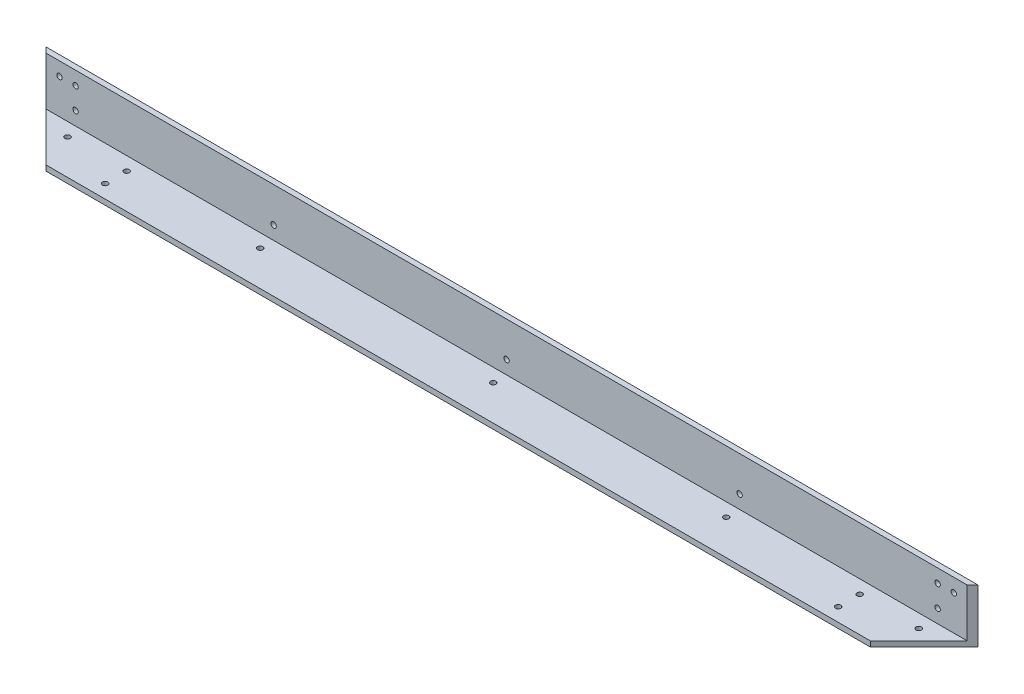
SolidWorks part; units mm, degrees
ref_plane "Front Plane" through (0, 0, 0) normal (0, 0, 1) x (1, 0, 0)
ref_plane "Top Plane" through (0, 0, 0) normal (0, 1, 0) x (1, 0, 0)
ref_plane "Right Plane" through (0, 0, 0) normal (1, 0, 0) x (0, 0, -1)
sketch "Sketch1" plane through (0, 0, 0) normal (1, 0, 0) x (0, 0, -1)
  line L0 (0, 0) -> (-31.75, 0)
  line L1 (-31.75, 0) -> (-31.75, 3.175)
  line L2 (-31.75, 3.175) -> (-3.175, 3.175)
  line L3 (-3.175, 3.175) -> (-3.175, 31.75)
  line L4 (-3.175, 31.75) -> (0, 31.75)
  line L5 (0, 31.75) -> (0, 0)
  dimension "LHeight" = 31.75
  dimension "LWidth" = 31.75
  dimension "LMaterialThickness" = 3.175
  dimension "D1" = 28.575
  dimension "D2" = 28.575
  dimension "D3" = 3.175
extrude "Boss-Extrude1" add sketch "Sketch1" along normal blind 550
chamfer "Chamfer6" distance 31.75 angle 45 1 edges at (550, 1.5875, 31.75)
chamfer "Chamfer7" distance 31.75 angle 45 1 edges at (0, 1.5875, 31.75)
sketch "TopHoles-Sketch3" plane through (0, 3.175, 0) normal (0, 1, 0) x (1, 0, 0)
  line L0 (518.25, -31.75) -> (31.75, -31.75) construction
  line L1 (518.25, -31.75) -> (31.75, -31.75) construction
  line L2 (550, 0) -> (0, 0) construction
  circle A5 centre (58.7375, -23.8125) radius 1.5875
  circle A6 centre (491.2625, -23.8125) radius 1.5875
  circle A9 centre (491.2625, -11.1125) radius 1.5875
  circle A10 centre (58.7375, -11.1125) radius 1.5875
  circle A11 centre (526.1875, -11.1125) radius 1.5875
  circle A12 centre (23.8125, -11.1125) radius 1.5875
  circle A13 centre (275, -11.1125) radius 1.5875
  circle A14 centre (137.5, -11.1125) radius 1.5875
  circle A15 centre (412.5, -11.1125) radius 1.5875
  dimension "D8" = 137.5
  dimension "D10" = 137.5
  dimension "D9" = 3.175
  dimension "D12" = 7.9375
  dimension "D2" = 11.1125
  dimension "D6" = 23.8125
  dimension "D3" = 23.8125
  dimension "D5" = 12.7
  dimension "D4" = 34.925
  dimension "D7" = 34.925
  dimension "D11" = 137.5
extrude "TopHoles-Cut-Extrude2" cut sketch "TopHoles-Sketch3" against normal through all
sketch "LeftHoles-Sketch4" plane through (0, 0, 3.175) normal (0, 0, 1) x (1, 0, 0)
  line L1 (550, 0) -> (0, 0) construction
  line L3 (550, 31.75) -> (0, 31.75) construction
  line L4 (0, 0) -> (0, 31.75) construction
  line L5 (550, 0) -> (550, 31.75) construction
  circle A1 centre (11.1125, 23.8125) radius 1.5875
  circle A3 centre (529.3625, 23.8125) radius 1.5875
  circle A4 centre (20.6375, 23.8125) radius 1.5875
  circle A5 centre (538.8875, 23.8125) radius 1.5875
  circle A7 centre (20.6375, 11.1125) radius 1.5875
  circle A8 centre (529.3625, 11.1125) radius 1.5875
  circle A10 centre (137.5, 11.1125) radius 1.5875
  circle A11 centre (275, 11.1125) radius 1.5875
  circle A12 centre (412.5, 11.1125) radius 1.5875
  dimension "D2" = 3.175
  dimension "D4" = 7.9375
  dimension "D1" = 11.1125
  dimension "D6" = 20.6375
  dimension "D3" = 11.1125
  dimension "D5" = 20.6375
  dimension "D8" = 137.5
  dimension "D9" = 137.5
  dimension "D10" = 137.5
  dimension "D7" = 11.1125
extrude "LeftHoles-Cut-Extrude3" cut sketch "LeftHoles-Sketch4" against normal through all
equation "\"TopRailWidth\"= 1.25in"
equation "\"TopRailHeight\"= 1.25in"
equation "\"RailThickness\"= .125in'Spec"
equation "\"SideRailHoleY1FromEdge\"= \"HoleOffsetFromEdge\""
equation "\"SideRailHoleX1FromSide\"= \"HoleOffsetFromSide\""
equation "\"SideRailLength\"= 550mm"
equation "\"VSWidth\"= 1.25in'Spec"
equation "\"HoleOffsetFromEdge\"= \"RailThickness\" * 2.5"
equation "\"HoleOffsetFromSide\"= \"RailThickness\" * 3.5"
equation "\"TopCBWidth\"= \"TopRailWidth\" - \"RailThickness\"'Equals 28.575"
equation "\"SideRailHoleX2FromSide\"= \"VSWidth\" - \"HoleOffsetFromEdge\" - \"RailThickness\"'Equals 20.6375"
equation "\"FasteningHoleDiameter\"= .125in"
equation "\"SideRailHoleY2FromSide\"= \"HoleOffsetFromSide\""
equation "\"D2@LeftHoles-Sketch4\"=\"FasteningHoleDiameter\""
equation "\"LWidth@Sketch1\"=\"TopRailWidth\""
equation "\"LHeight@Sketch1\"=\"TopRailHeight\""
equation "\"LMaterialThickness@Sketch1\"=\"RailThickness\""
equation "\"D1@Boss-Extrude1\"=\"SideRailLength\""
equation "\"D2@TopHoles-Sketch3\"=\"TopHoleY1FromSide\""
equation "\"D9@TopHoles-Sketch3\" = \"FasteningHoleDiameter\""
equation "\"D4@LeftHoles-Sketch4\"=\"SideRailHoleY1FromEdge\""
equation "\"D1@Chamfer6\"=\"TopRailWidth\""
equation "\"D1@Chamfer7\"=\"TopRailWidth\""
equation "\"D1@LeftHoles-Sketch4\"=\"SideRailHoleX1FromSide\""
equation "\"D6@LeftHoles-Sketch4\"=\"SideRailHoleX2FromSide\""
equation "\"D5@LeftHoles-Sketch4\"=\"SideRailHoleX2FromSide\""
equation "\"TopHoleY1FromSide\"= \"HoleOffsetFromSide\""
equation "\"TopHoleY2FromY1\"= \"TopCBWidth\" - \"TopHoleY1FromEdge\" - \"HoleOffsetFromEdge\"'Equals 12.7"
equation "\"TopHoleX1FromEdge\"= \"TopCBWidth\" - \"HoleOffsetFromEdge\"'Equals 20.6375"
equation "\"TopHoleX2FromX1\"= \"TopCBLength\" - \"TopHoleX1FromEdge\" - \"HoleOffsetFromEdge\"'Equals 34.925"
equation "\"D5@TopHoles-Sketch3\"=\"TopHoleY2FromY1\""
equation "\"D4@TopHoles-Sketch3\"=\"TopHoleX2FromX1\""
equation "\"D7@TopHoles-Sketch3\"=\"TopHoleX2FromX1\""
equation "\"D3@TopHoles-Sketch3\"=\"TopHoleX1FromEdge\" + \"RailThickness\""
equation "\"D6@TopHoles-Sketch3\"=\"TopHoleX1FromEdge\" + \"RailThickness\""
equation "\"TopCBLength\"= \"TopRailWidth\" * 2'Equals 63.5"
equation "\"TopHoleY1FromEdge\"= \"HoleOffsetFromEdge\""
equation "\"LeftOrRightEnclosureHoleOffsets\"= \"SideRailLength\" / 4"
equation "\"D8@TopHoles-Sketch3\"=\"LeftOrRightEnclosureHoleOffsets\""
equation "\"D10@TopHoles-Sketch3\"=\"LeftOrRightEnclosureHoleOffsets\""
equation "\"D11@TopHoles-Sketch3\"=\"LeftOrRightEnclosureHoleOffsets\""
equation "\"D8@LeftHoles-Sketch4\"=\"LeftOrRightEnclosureHoleOffsets\""
equation "\"D9@LeftHoles-Sketch4\"=\"LeftOrRightEnclosureHoleOffsets\""
equation "\"D10@LeftHoles-Sketch4\"=\"LeftOrRightEnclosureHoleOffsets\""
equation "\"D7@LeftHoles-Sketch4\"=\"SideRailHoleY2FromSide\""
